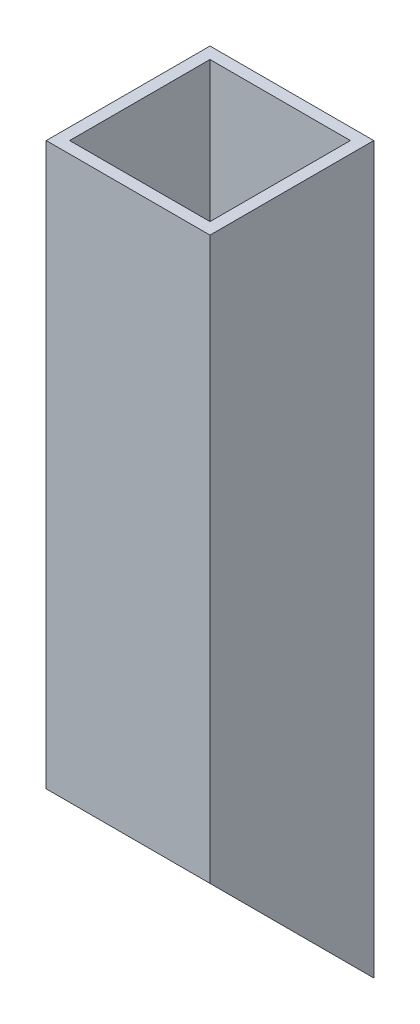
SolidWorks part; units mm, degrees
material "6063-T6"
ref_plane "Front Plane" through (0, 0, 0) normal (0, 0, 1) x (1, 0, 0)
ref_plane "Top Plane" through (0, 0, 0) normal (0, 1, 0) x (1, 0, 0)
ref_plane "Right Plane" through (0, 0, 0) normal (1, 0, 0) x (0, 0, -1)
sketch "Sketch1" plane through (0, 0, 0) normal (0, 1, 0) x (1, 0, 0)
  line L0 (41.275, 3.175) -> (41.275, 41.275)
  line L1 (0, 0) -> (44.45, 0)
  line L2 (0, 0) -> (0, 44.45)
  line L3 (0, 44.45) -> (44.45, 44.45)
  line L4 (44.45, 0) -> (44.45, 44.45)
  line L5 (3.175, 41.275) -> (41.275, 41.275)
  line L6 (3.175, 3.175) -> (3.175, 41.275)
  line L7 (3.175, 3.175) -> (41.275, 3.175)
  dimension "D1" = 44.45
  dimension "D2" = 3.175
extrude "Boss-Extrude1" add sketch "Sketch1" along normal blind 196.85
chamfer "Chamfer1" distance 44.45 angle 45 1 edges at (22.225, 0, 0)
